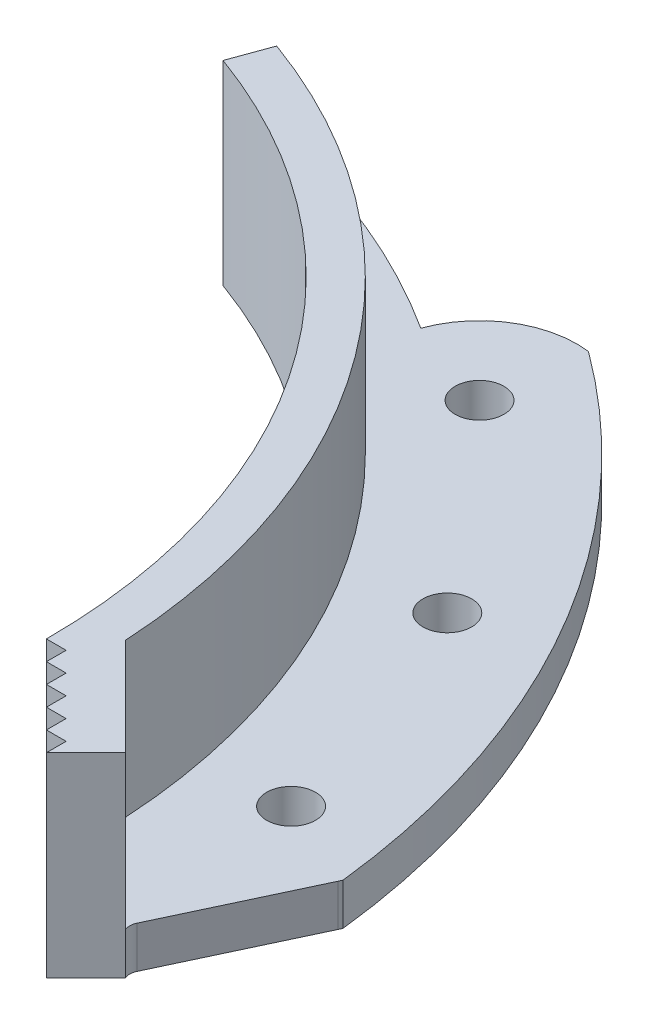
SolidWorks part; units mm, degrees
ref_plane "Спереди" through (0, 0, 0) normal (0, 0, 1) x (1, 0, 0)
ref_plane "Сверху" through (0, 0, 0) normal (0, 1, 0) x (1, 0, 0)
ref_plane "Справа" through (0, 0, 0) normal (1, 0, 0) x (0, 0, -1)
sketch "Эскиз1" plane through (0, 0, 0) normal (0, 1, 0) x (1, 0, 0)
  line L0 (0, 0) -> (34.7105, 41.3664) construction
  line L1 (0, 0) -> (46.7654, 27) construction
  line L2 (0, 0) -> (53.1796, 9.377) construction
  line L3 (0, 0) -> (0, 53.6075) construction
  line L4 (15.3909, 42.2862) -> (17.785, 48.864)
  line L5 (0, 0) -> (52, 0) construction
  line L6 (44.329, 7.7422) -> (52, 0.0712) construction
  line L7 (0, 0) -> (20.2161, 55.5433) construction
  line L8 (0, 45) -> (52.0711, -7.0709) construction
  line L10 (52.0711, -7.0709) -> (54.1924, -4.9496) construction
  line L11 (54.1924, -4.9496) -> (59.5173, 6.4048)
  line L12 (54.1924, -4.9496) -> (44.778, 4.4648)
  arc A0 (45, 0) -> (0, 45) centre (0, 0) ccw construction
  circle A1 centre (0, 0) radius 54 construction
  circle A2 centre (34.7105, 41.3664) radius 1.75
  circle A3 centre (46.7654, 27) radius 1.75
  circle A4 centre (53.1796, 9.377) radius 1.75
  arc A5 (52, 0) -> (0, 52) centre (0, 0) ccw construction
  arc A6 (44.778, 4.4648) -> (15.3909, 42.2862) centre (0, 0) ccw
  arc A7 (59.5173, 6.4048) -> (60.0733, 10.5925) centre (53.1796, 9.377) ccw
  arc A8 (39.21, 46.7287) -> (28.1245, 43.738) centre (34.7105, 41.3664) ccw
  arc A10 (48.6252, 4.0613) -> (51.9405, 2.4876) centre (53.1796, 9.377) ccw construction
  arc A11 (28.1245, 43.738) -> (17.785, 48.864) centre (0, 0) ccw
  arc A14 (60.0733, 10.5925) -> (39.21, 46.7287) centre (0, 0) ccw
  dimension "D6" = 40
  dimension "D7" = 60
  dimension "D1" = 3.5
  dimension "D2" = 3.5
  dimension "D3" = 3.5
  dimension "D4" = 90
  dimension "D5" = 108
  dimension "D9" = 104
  dimension "D10" = 20
  dimension "D11" = 14
  dimension "D13" = 14
  dimension "D8" = 80
  dimension "D14" = 5
extrude "Бобышка-Вытянуть1" add sketch "Эскиз1" along normal blind 3
sketch "Эскиз2" plane through (0, 3, 0) normal (0, 1, 0) x (1, 0, 0)
  line L0 (17.785, 48.864) -> (15.3909, 42.2862) construction
  line L1 (52.0711, -7.0711) -> (52.0711, -5.6569)
  line L2 (15.3909, 42.2862) -> (16.417, 45.1052)
  line L3 (52.0711, -7.0711) -> (54.8995, -4.2426)
  line L4 (0, 45) -> (45, 0) construction
  line L5 (45, 0) -> (52.0711, -7.0711) construction
  line L6 (54.8995, -4.2426) -> (47.922, 2.7348)
  line L7 (52.0711, -5.6569) -> (50.6569, -5.6569)
  line L8 (50.6569, -4.2426) -> (49.2426, -4.2426)
  line L9 (50.6569, -5.6569) -> (50.6569, -4.2426)
  line L10 (49.2426, -2.8284) -> (47.8284, -2.8284)
  line L11 (49.2426, -4.2426) -> (49.2426, -2.8284)
  line L12 (47.8284, -1.4142) -> (46.4142, -1.4142)
  line L13 (47.8284, -2.8284) -> (47.8284, -1.4142)
  line L14 (46.4142, 0) -> (45, 0)
  line L15 (46.4142, -1.4142) -> (46.4142, 0)
  arc A0 (45, 0) -> (15.3909, 42.2862) centre (0, 0) ccw
  arc A1 (47.922, 2.7348) -> (16.417, 45.1052) centre (0, 0) ccw
  circle A2 centre (0, 0) radius 45 construction
  dimension "D1" = 48
  dimension "D2" = 45
  dimension "D3" = 1
  dimension "D4" = 1
  dimension "D5" = 5
  dimension "D6" = 4
extrude "Бобышка-Вытянуть2" add sketch "Эскиз2" along normal blind 11 and the other way blind 3
sketch "Эскиз4" plane through (0, 3, 0) normal (0, 1, 0) x (1, 0, 0)
  circle A0 centre (0, 0) radius 60
  circle A1 centre (0, 0) radius 75.7374
  dimension "D1" = 120
extrude "Вырез-Вытянуть1" cut sketch "Эскиз4" against normal through all and the other way through all
fillet "Скругление1" radius 1 1 edges at (54.6438, 1.5, 3.987)
